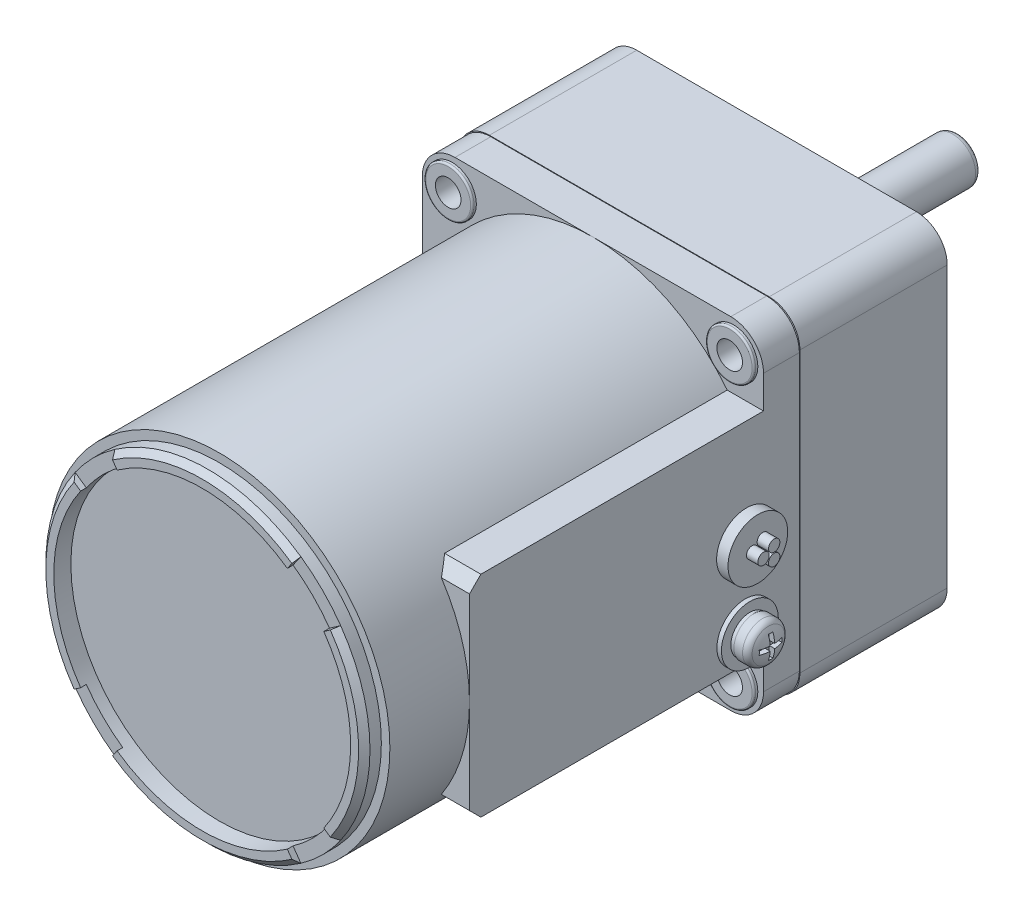
SolidWorks part; units mm, degrees
ref_plane "前视基准面" through (0, 0, 0) normal (0, 0, 1) x (1, 0, 0)
ref_plane "上视基准面" through (0, 0, 0) normal (0, 1, 0) x (1, 0, 0)
ref_plane "右视基准面" through (0, 0, 0) normal (1, 0, 0) x (0, 0, -1)
ref_plane "基准面4" through (0, 0, 0) normal (0, 0, 1) x (1, 0, 0)
sketch "草图1" plane through (0, 0, 0) normal (0, 0, 1) x (1, 0, 0)
  line L0 (-30, 24.6) -> (-30, -24.6)
  line L1 (-24.6, -30) -> (24.6, -30)
  line L2 (30, -24.6) -> (30, 24.6)
  line L3 (24.6, 30) -> (-24.6, 30)
  arc A0 (-30, -24.6) -> (-24.6, -30) centre (-24.6, -24.6) ccw
  arc A1 (24.6, -30) -> (30, -24.6) centre (24.6, -24.6) ccw
  arc A2 (30, 24.6) -> (24.6, 30) centre (24.6, 24.6) ccw
  arc A3 (-24.6, 30) -> (-30, 24.6) centre (-24.6, 24.6) ccw
extrude "凸台-拉伸1" add sketch "草图1" along normal blind 26
ref_plane "基准面5" through (0, 0, 0) normal (1, 0, 0) x (0, 0, -1)
sketch "草图2" plane through (0, 0, 0) normal (1, 0, 0) x (0, 0, -1)
  line L0 (0, 10) -> (0, 22.5)
  line L1 (0, 22.5) -> (5, 22.5)
  line L2 (6, 21.5) -> (6, 14)
  line L3 (6, 14) -> (31, 14)
  line L4 (32, 13) -> (32, 10)
  line L5 (32, 10) -> (0, 10)
  line L6 (32, 10) -> (0, 10) construction
  arc A0 (5, 22.5) -> (6, 21.5) centre (5, 21.5) cw
  arc A1 (31, 14) -> (32, 13) centre (31, 13) cw
revolve "旋转1" add sketch "草图2" angle 360 about L6 reverse direction yes
ref_plane "基准面6" through (0, 0, 26) normal (0, 0, 1) x (1, 0, 0)
sketch "草图3" plane through (0, 0, 26) normal (0, 0, 1) x (1, 0, 0)
  line L0 (-30, 24.25) -> (-30, -24.25)
  line L1 (-24.25, -30) -> (24.25, -30)
  line L2 (30, -24.25) -> (30, 24.25)
  line L3 (24.25, 30) -> (-24.25, 30)
  arc A0 (-30, -24.25) -> (-24.25, -30) centre (-24.25, -24.25) ccw
  arc A1 (24.25, -30) -> (30, -24.25) centre (24.25, -24.25) ccw
  arc A2 (30, 24.25) -> (24.25, 30) centre (24.25, 24.25) ccw
  arc A3 (-24.25, 30) -> (-30, 24.25) centre (-24.25, 24.25) ccw
extrude "凸台-拉伸2" add sketch "草图3" along normal blind 6.3
sketch "草图4" plane through (0, 0, 26) normal (0, 0, 1) x (1, 0, 0)
  line L0 (-30, 30) -> (-30, -30)
  line L1 (-30, -30) -> (30, -30)
  line L2 (30, -30) -> (30, 30)
  line L3 (30, 30) -> (-30, 30)
  line L4 (-29, 24.25) -> (-29, -24.25)
  line L5 (-24.25, -29) -> (24.25, -29)
  line L6 (29, -24.25) -> (29, 24.25)
  line L7 (24.25, 29) -> (-24.25, 29)
  arc A0 (-29, -24.25) -> (-24.25, -29) centre (-24.25, -24.25) ccw
  arc A1 (24.25, -29) -> (29, -24.25) centre (24.25, -24.25) ccw
  arc A2 (29, 24.25) -> (24.25, 29) centre (24.25, 24.25) ccw
  arc A3 (-24.25, 29) -> (-29, 24.25) centre (-24.25, 24.25) ccw
extrude "切除-拉伸1" cut sketch "草图4" against normal blind 0.1
ref_plane "基准面7" through (0, 0, 0) normal (1, 0, 0) x (0, 0, -1)
sketch "草图5" plane through (0, 0, 0) normal (1, 0, 0) x (0, 0, -1)
  line L0 (-98, 0) -> (-98, 26.1)
  line L1 (-98, 26.1) -> (-101, 26.1)
  line L2 (-101, 26.1) -> (-101, 27.5)
  line L3 (-101, 27.5) -> (-100, 28.5)
  line L4 (-100, 28.5) -> (-98, 28.5)
  line L5 (-98, 28.5) -> (-98, 30)
  line L6 (-98, 30) -> (-32.3, 30)
  line L7 (-32.3, 30) -> (-32.3, 0)
  line L8 (-32.3, 0) -> (-98, 0)
  line L9 (-32.3, 0) -> (-101, 0) construction
revolve "旋转2" add sketch "草图5" angle 360 about L9 reverse direction yes
ref_plane "基准面8" through (0, 0, 101) normal (0, 0, 1) x (1, 0, 0)
sketch "草图6" plane through (0, 0, 101) normal (0, 0, 1) x (1, 0, 0)
  line L0 (-21.3799, -14.9703) -> (-23.3458, -16.3469)
  line L1 (-16.3469, -23.3458) -> (-14.9703, -21.3799)
  line L2 (14.9703, -21.3799) -> (16.3469, -23.3458)
  line L3 (23.3458, -16.3469) -> (21.3799, -14.9703)
  line L4 (21.3799, 14.9703) -> (23.3458, 16.3469)
  line L5 (16.3469, 23.3458) -> (14.9703, 21.3799)
  line L6 (-14.9703, 21.3799) -> (-16.3469, 23.3458)
  line L7 (-23.3458, 16.3469) -> (-21.3799, 14.9703)
  arc A0 (-21.3799, 14.9703) -> (-21.3799, -14.9703) centre (0, 0) ccw
  arc A1 (-23.3458, -16.3469) -> (-16.3469, -23.3458) centre (0, 0) ccw
  arc A2 (-14.9703, -21.3799) -> (14.9703, -21.3799) centre (0, 0) ccw
  arc A3 (16.3469, -23.3458) -> (23.3458, -16.3469) centre (0, 0) ccw
  arc A4 (21.3799, -14.9703) -> (21.3799, 14.9703) centre (0, 0) ccw
  arc A5 (23.3458, 16.3469) -> (16.3469, 23.3458) centre (0, 0) ccw
  arc A6 (14.9703, 21.3799) -> (-14.9703, 21.3799) centre (0, 0) ccw
  arc A7 (-16.3469, 23.3458) -> (-23.3458, 16.3469) centre (0, 0) ccw
extrude "切除-拉伸2" cut sketch "草图6" against normal blind 1
ref_plane "基准面9" through (30, 0, 0) normal (1, 0, 0) x (0, 0, -1)
sketch "草图7" plane through (30, 0, 0) normal (1, 0, 0) x (0, 0, -1)
  line L0 (-84, -16.5) -> (-82, -18.5)
  line L1 (-82, -18.5) -> (-26, -18.5)
  line L2 (-26, -18.5) -> (-26, 18.5)
  line L3 (-26, 18.5) -> (-82, 18.5)
  line L4 (-82, 18.5) -> (-84, 16.5)
  line L5 (-84, 16.5) -> (-84, -16.5)
extrude "凸台-拉伸3" add sketch "草图7" against normal blind 30
ref_plane "基准面10" through (0, 0, 0) normal (0.7071, 0.7071, 0) x (0, 0, -1)
sketch "草图8" plane through (0, 0, 0) normal (0.7071, 0.7071, 0) x (0, 0, -1)
  line L0 (-33, -35) -> (-33, -31.05)
  line L1 (-32.7, -30.75) -> (-32.3, -30.75)
  line L2 (-32.3, -30.75) -> (-32.3, -35)
  line L3 (-32.3, -35) -> (-33, -35)
  line L4 (-32.3, -35) -> (-33, -35) construction
  arc A0 (-33, -31.05) -> (-32.7, -30.75) centre (-32.7, -31.05) cw
revolve "旋转3" add sketch "草图8" angle 360 about L4 reverse direction yes
ref_plane "基准面11" through (0, 0, 32.3) normal (0, 0, 1) x (1, 0, 0)
sketch "草图9" plane through (0, 0, 0) normal (0, 0, 1) x (1, 0, 0)
  line L0 (24.7487, -24.7487) -> (24.7487, 975.2513)
  line L1 (24.7487, -24.7487) -> (-975.2513, -24.7487)
pattern_linear "阵列(线性)1" count 2 spacing 49.4975 along (0, 1, 0) count 2 spacing 49.4975 along (-1, 0, 0) of "旋转3"
ref_plane "基准面12" through (0, 0, 0) normal (0, 1, 0) x (1, 0, 0)
sketch "草图10" plane through (0, 0, 0) normal (0, 1, 0) x (1, 0, 0)
  line L0 (32, -35.3) -> (32, -40.55)
  line L1 (32, -40.55) -> (30, -40.55)
  line L2 (30, -40.55) -> (30, -35.3)
  line L3 (30, -35.3) -> (32, -35.3)
  line L4 (30, -35.3) -> (32, -35.3) construction
revolve "旋转4" add sketch "草图10" angle 360 about L4 reverse direction yes
ref_plane "基准面13" through (32, 0, 0) normal (1, 0, 0) x (0, 0, -1)
sketch "草图11" plane through (32, 0, 0) normal (1, 0, 0) x (0, 0, -1)
  circle A0 centre (-36.3, 0) radius 1
extrude "凸台-拉伸4" add sketch "草图11" along normal blind 2
ref_plane "基准面14" through (32, 0, 0) normal (1, 0, 0) x (0, 0, -1)
sketch "草图12" plane through (32, 0, 0) normal (1, 0, 0) x (0, 0, -1)
  circle A0 centre (-34.425, -1.0825) radius 1
extrude "凸台-拉伸5" add sketch "草图12" along normal blind 2
ref_plane "基准面15" through (32, 0, 0) normal (1, 0, 0) x (0, 0, -1)
sketch "草图13" plane through (32, 0, 0) normal (1, 0, 0) x (0, 0, -1)
  circle A0 centre (-34.425, 1.0825) radius 1
extrude "凸台-拉伸6" add sketch "草图13" along normal blind 2
ref_plane "基准面16" through (0, -13.5, 0) normal (0, 1, 0) x (1, 0, 0)
sketch "草图14" plane through (0, -13.5, 0) normal (0, 1, 0) x (1, 0, 0)
  line L0 (33.0131, -39) -> (31.5, -39)
  line L1 (31.5, -39) -> (31.5, -38.85)
  line L2 (31.5, -38.85) -> (30.8, -38.85)
  line L3 (30.8, -38.85) -> (30.8, -40.5)
  line L4 (30.8, -40.5) -> (30, -40.5)
  line L5 (30, -40.5) -> (30, -35.5)
  line L6 (30, -35.5) -> (34.8, -35.5)
  line L7 (30, -35.5) -> (34.8, -35.5) construction
  arc A0 (34.8, -35.5) -> (34.0663, -38.375) centre (28.8, -35.5) cw
  arc A1 (34.0663, -38.375) -> (33.0131, -39) centre (33.0131, -37.8) cw
revolve "旋转5" add sketch "草图14" angle 360 about L7 reverse direction yes
ref_plane "基准面17" through (34.8, 0, 0) normal (1, 0, 0) x (0, 0, -1)
sketch "草图15" plane through (34.8, 0, 0) normal (1, 0, 0) x (0, 0, -1)
  line L0 (-37.5, -13.1) -> (-37.5, -13.9)
  line L1 (-37.5, -13.9) -> (-35.9, -13.9)
  line L2 (-35.9, -13.9) -> (-35.9, -15.5)
  line L3 (-35.9, -15.5) -> (-35.1, -15.5)
  line L4 (-35.1, -15.5) -> (-35.1, -13.9)
  line L5 (-35.1, -13.9) -> (-33.5, -13.9)
  line L6 (-33.5, -13.9) -> (-33.5, -13.1)
  line L7 (-33.5, -13.1) -> (-35.1, -13.1)
  line L8 (-35.1, -13.1) -> (-35.1, -11.5)
  line L9 (-35.1, -11.5) -> (-35.9, -11.5)
  line L10 (-35.9, -11.5) -> (-35.9, -13.1)
  line L11 (-35.9, -13.1) -> (-37.5, -13.1)
extrude "切除-拉伸3" cut sketch "草图15" against normal blind 1
ref_plane "基准面18" through (0, 0, 0) normal (0.7071, 0.7071, 0) x (0, 0, -1)
sketch "草图16" plane through (0, 0, 0) normal (0.7071, 0.7071, 0) x (0, 0, -1)
  line L0 (-33, -35) -> (-33, -32.75)
  line L1 (-33, -32.75) -> (0, -32.75)
  line L2 (0, -32.75) -> (0, -35)
  line L3 (0, -35) -> (-33, -35)
  line L4 (0, -35) -> (-33, -35) construction
revolve "切除-旋转1" cut sketch "草图16" angle 360 about L4 reverse direction yes
ref_plane "基准面19" through (0, 0, 33) normal (0, 0, 1) x (1, 0, 0)
sketch "草图17" plane through (0, 0, 0) normal (0, 0, 1) x (1, 0, 0)
  line L0 (24.7487, -24.7487) -> (24.7487, 975.2513)
  line L1 (24.7487, -24.7487) -> (-975.2513, -24.7487)
pattern_linear "阵列(线性)2" count 2 spacing 49.4975 along (0, 1, 0) count 2 spacing 49.4975 along (-1, 0, 0) of "切除-旋转1"
ref_plane "基准面20" through (0, 0, 0) normal (0, 0, 1) x (1, 0, 0)
ref_plane "基准面21" through (0, 0, 0) normal (0, 0, 1) x (1, 0, 0)
ref_plane "基准面22" through (0, 0, 34.8) normal (0, 0, 1) x (1, 0, 0)
ref_plane "基准面23" through (0, 0, 33) normal (0, 0, 1) x (1, 0, 0)
ref_plane "基准面24" through (0, 0, 34.8) normal (0, 0, 1) x (1, 0, 0)
ref_plane "to_motor XY" through (0, 0, 0) normal (0, 0, -1) x (-1, 0, 0)
ref_plane "to_motor XZ" through (0, 10, 0) normal (0, 1, 0) x (1, 0, 0)
ref_plane "to_motor YZ" through (0, 0, 0) normal (1, 0, 0) x (0, 0, -1)
ref_axis "to_motor X" through (-80.9, 10, 0) along (1, 0, 0)
ref_axis "to_motor Y" through (0, 50, 0) along (0, -1, 0)
ref_axis "to_motor Z" through (0, 10, -80.9) along (0, 0, 1)
sketch3d "to_motor"
  point P0 (0, 10, 0)
ref_plane "to_motor_r XY" through (0, 0, 0) normal (0, 0, -1) x (-1, 0, 0)
ref_plane "to_motor_r XZ" through (0, -10, 0) normal (0, 1, 0) x (1, 0, 0)
ref_plane "to_motor_r YZ" through (0, 0, 0) normal (1, 0, 0) x (0, 0, -1)
ref_axis "to_motor_r X" through (-80.9, -10, 0) along (1, 0, 0)
ref_axis "to_motor_r Y" through (0, 50, 0) along (0, -1, 0)
ref_axis "to_motor_r Z" through (0, -10, -80.9) along (0, 0, 1)
sketch3d "to_motor_r"
  point P0 (0, -10, 0)
ref_plane "to_bolt_inner4 XY" through (0, 0, 0) normal (0, 0, -1) x (-1, 0, 0)
ref_plane "to_bolt_inner4 XZ" through (0, 24.7487, 0) normal (0, 1, 0) x (1, 0, 0)
ref_plane "to_bolt_inner4 YZ" through (-24.7487, 0, 0) normal (1, 0, 0) x (0, 0, -1)
ref_axis "to_bolt_inner4 X" through (-80.9, 24.7487, 0) along (1, 0, 0)
ref_axis "to_bolt_inner4 Y" through (-24.7487, 50, 0) along (0, -1, 0)
ref_axis "to_bolt_inner4 Z" through (-24.7487, 24.7487, -80.9) along (0, 0, 1)
sketch3d "to_bolt_inner4"
  point P0 (-24.7487, 24.7487, 0)
ref_plane "to_bolt_inner2 XY" through (0, 0, 0) normal (0, 0, -1) x (-1, 0, 0)
ref_plane "to_bolt_inner2 XZ" through (0, -24.7487, 0) normal (0, 1, 0) x (1, 0, 0)
ref_plane "to_bolt_inner2 YZ" through (-24.7487, 0, 0) normal (1, 0, 0) x (0, 0, -1)
ref_axis "to_bolt_inner2 X" through (-80.9, -24.7487, 0) along (1, 0, 0)
ref_axis "to_bolt_inner2 Y" through (-24.7487, 50, 0) along (0, -1, 0)
ref_axis "to_bolt_inner2 Z" through (-24.7487, -24.7487, -80.9) along (0, 0, 1)
sketch3d "to_bolt_inner2"
  point P0 (-24.7487, -24.7487, 0)
ref_plane "to_bolt_inner3 XY" through (0, 0, 0) normal (0, 0, -1) x (-1, 0, 0)
ref_plane "to_bolt_inner3 XZ" through (0, -24.7487, 0) normal (0, 1, 0) x (1, 0, 0)
ref_plane "to_bolt_inner3 YZ" through (24.7487, 0, 0) normal (1, 0, 0) x (0, 0, -1)
ref_axis "to_bolt_inner3 X" through (-80.9, -24.7487, 0) along (1, 0, 0)
ref_axis "to_bolt_inner3 Y" through (24.7487, 50, 0) along (0, -1, 0)
ref_axis "to_bolt_inner3 Z" through (24.7487, -24.7487, -80.9) along (0, 0, 1)
sketch3d "to_bolt_inner3"
  point P0 (24.7487, -24.7487, 0)
ref_plane "to_bolt_inner1 XY" through (0, 0, 0) normal (0, 0, -1) x (-1, 0, 0)
ref_plane "to_bolt_inner1 XZ" through (0, 24.7487, 0) normal (0, 1, 0) x (1, 0, 0)
ref_plane "to_bolt_inner1 YZ" through (24.7487, 0, 0) normal (1, 0, 0) x (0, 0, -1)
ref_axis "to_bolt_inner1 X" through (-80.9, 24.7487, 0) along (1, 0, 0)
ref_axis "to_bolt_inner1 Y" through (24.7487, 50, 0) along (0, -1, 0)
ref_axis "to_bolt_inner1 Z" through (24.7487, 24.7487, -80.9) along (0, 0, 1)
sketch3d "to_bolt_inner1"
  point P0 (24.7487, 24.7487, 0)
ref_plane "to_bolt_outer4 XY" through (0, 0, 34.8) normal (0, 0, 1) x (1, 0, 0)
ref_plane "to_bolt_outer4 XZ" through (0, 24.7487, 0) normal (0, -1, 0) x (-1, 0, 0)
ref_plane "to_bolt_outer4 YZ" through (-24.7487, 0, 0) normal (1, 0, 0) x (0, 0, -1)
ref_axis "to_bolt_outer4 X" through (-80.9, 24.7487, 34.8) along (1, 0, 0)
ref_axis "to_bolt_outer4 Y" through (-24.7487, -50, 34.8) along (0, 1, 0)
ref_axis "to_bolt_outer4 Z" through (-24.7487, 24.7487, 80.9) along (0, 0, -1)
sketch3d "to_bolt_outer4"
  point P0 (-24.7487, 24.7487, 34.8)
ref_plane "to_bolt_outer2 XY" through (0, 0, 34.8) normal (0, 0, 1) x (1, 0, 0)
ref_plane "to_bolt_outer2 XZ" through (0, -24.7487, 0) normal (0, -1, 0) x (-1, 0, 0)
ref_plane "to_bolt_outer2 YZ" through (-24.7487, 0, 0) normal (1, 0, 0) x (0, 0, -1)
ref_axis "to_bolt_outer2 X" through (-80.9, -24.7487, 34.8) along (1, 0, 0)
ref_axis "to_bolt_outer2 Y" through (-24.7487, -50, 34.8) along (0, 1, 0)
ref_axis "to_bolt_outer2 Z" through (-24.7487, -24.7487, 80.9) along (0, 0, -1)
sketch3d "to_bolt_outer2"
  point P0 (-24.7487, -24.7487, 34.8)
ref_plane "to_bolt_outer3 XY" through (0, 0, 34.8) normal (0, 0, 1) x (1, 0, 0)
ref_plane "to_bolt_outer3 XZ" through (0, -24.7487, 0) normal (0, -1, 0) x (-1, 0, 0)
ref_plane "to_bolt_outer3 YZ" through (24.7487, 0, 0) normal (1, 0, 0) x (0, 0, -1)
ref_axis "to_bolt_outer3 X" through (-80.9, -24.7487, 34.8) along (1, 0, 0)
ref_axis "to_bolt_outer3 Y" through (24.7487, -50, 34.8) along (0, 1, 0)
ref_axis "to_bolt_outer3 Z" through (24.7487, -24.7487, 80.9) along (0, 0, -1)
sketch3d "to_bolt_outer3"
  point P0 (24.7487, -24.7487, 34.8)
ref_plane "to_bolt_outer1 XY" through (0, 0, 34.8) normal (0, 0, 1) x (1, 0, 0)
ref_plane "to_bolt_outer1 XZ" through (0, 24.7487, 0) normal (0, -1, 0) x (-1, 0, 0)
ref_plane "to_bolt_outer1 YZ" through (24.7487, 0, 0) normal (1, 0, 0) x (0, 0, -1)
ref_axis "to_bolt_outer1 X" through (-80.9, 24.7487, 34.8) along (1, 0, 0)
ref_axis "to_bolt_outer1 Y" through (24.7487, -50, 34.8) along (0, 1, 0)
ref_axis "to_bolt_outer1 Z" through (24.7487, 24.7487, 80.9) along (0, 0, -1)
sketch3d "to_bolt_outer1"
  point P0 (24.7487, 24.7487, 34.8)
ref_plane "to_washer1 XY" through (0, 0, 33) normal (0, 0, 1) x (1, 0, 0)
ref_plane "to_washer1 XZ" through (0, 24.7487, 0) normal (0, -1, 0) x (-1, 0, 0)
ref_plane "to_washer1 YZ" through (24.7487, 0, 0) normal (1, 0, 0) x (0, 0, -1)
ref_axis "to_washer1 X" through (-80.9, 24.7487, 33) along (1, 0, 0)
ref_axis "to_washer1 Y" through (24.7487, -50, 33) along (0, 1, 0)
ref_axis "to_washer1 Z" through (24.7487, 24.7487, 80.9) along (0, 0, -1)
sketch3d "to_washer1"
  point P0 (24.7487, 24.7487, 33)
ref_plane "to_washer3 XY" through (0, 0, 33) normal (0, 0, 1) x (1, 0, 0)
ref_plane "to_washer3 XZ" through (0, -24.7487, 0) normal (0, -1, 0) x (-1, 0, 0)
ref_plane "to_washer3 YZ" through (24.7487, 0, 0) normal (1, 0, 0) x (0, 0, -1)
ref_axis "to_washer3 X" through (-80.9, -24.7487, 33) along (1, 0, 0)
ref_axis "to_washer3 Y" through (24.7487, -50, 33) along (0, 1, 0)
ref_axis "to_washer3 Z" through (24.7487, -24.7487, 80.9) along (0, 0, -1)
sketch3d "to_washer3"
  point P0 (24.7487, -24.7487, 33)
ref_plane "to_washer2 XY" through (0, 0, 33) normal (0, 0, 1) x (1, 0, 0)
ref_plane "to_washer2 XZ" through (0, -24.7487, 0) normal (0, -1, 0) x (-1, 0, 0)
ref_plane "to_washer2 YZ" through (-24.7487, 0, 0) normal (1, 0, 0) x (0, 0, -1)
ref_axis "to_washer2 X" through (-80.9, -24.7487, 33) along (1, 0, 0)
ref_axis "to_washer2 Y" through (-24.7487, -50, 33) along (0, 1, 0)
ref_axis "to_washer2 Z" through (-24.7487, -24.7487, 80.9) along (0, 0, -1)
sketch3d "to_washer2"
  point P0 (-24.7487, -24.7487, 33)
ref_plane "to_washer4 XY" through (0, 0, 33) normal (0, 0, 1) x (1, 0, 0)
ref_plane "to_washer4 XZ" through (0, 24.7487, 0) normal (0, -1, 0) x (-1, 0, 0)
ref_plane "to_washer4 YZ" through (-24.7487, 0, 0) normal (1, 0, 0) x (0, 0, -1)
ref_axis "to_washer4 X" through (-80.9, 24.7487, 33) along (1, 0, 0)
ref_axis "to_washer4 Y" through (-24.7487, -50, 33) along (0, 1, 0)
ref_axis "to_washer4 Z" through (-24.7487, 24.7487, 80.9) along (0, 0, -1)
sketch3d "to_washer4"
  point P0 (-24.7487, 24.7487, 33)
ref_plane "to_nut4 XY" through (0, 0, 34.8) normal (0, 0, 1) x (1, 0, 0)
ref_plane "to_nut4 XZ" through (0, 24.7487, 0) normal (0, -1, 0) x (-1, 0, 0)
ref_plane "to_nut4 YZ" through (-24.7487, 0, 0) normal (1, 0, 0) x (0, 0, -1)
ref_axis "to_nut4 X" through (-80.9, 24.7487, 34.8) along (1, 0, 0)
ref_axis "to_nut4 Y" through (-24.7487, -50, 34.8) along (0, 1, 0)
ref_axis "to_nut4 Z" through (-24.7487, 24.7487, 80.9) along (0, 0, -1)
sketch3d "to_nut4"
  point P0 (-24.7487, 24.7487, 34.8)
ref_plane "to_nut1 XY" through (0, 0, 34.8) normal (0, 0, 1) x (1, 0, 0)
ref_plane "to_nut1 XZ" through (0, 24.7487, 0) normal (0, -1, 0) x (-1, 0, 0)
ref_plane "to_nut1 YZ" through (24.7487, 0, 0) normal (1, 0, 0) x (0, 0, -1)
ref_axis "to_nut1 X" through (-80.9, 24.7487, 34.8) along (1, 0, 0)
ref_axis "to_nut1 Y" through (24.7487, -50, 34.8) along (0, 1, 0)
ref_axis "to_nut1 Z" through (24.7487, 24.7487, 80.9) along (0, 0, -1)
sketch3d "to_nut1"
  point P0 (24.7487, 24.7487, 34.8)
ref_plane "to_nut3 XY" through (0, 0, 34.8) normal (0, 0, 1) x (1, 0, 0)
ref_plane "to_nut3 XZ" through (0, -24.7487, 0) normal (0, -1, 0) x (-1, 0, 0)
ref_plane "to_nut3 YZ" through (24.7487, 0, 0) normal (1, 0, 0) x (0, 0, -1)
ref_axis "to_nut3 X" through (-80.9, -24.7487, 34.8) along (1, 0, 0)
ref_axis "to_nut3 Y" through (24.7487, -50, 34.8) along (0, 1, 0)
ref_axis "to_nut3 Z" through (24.7487, -24.7487, 80.9) along (0, 0, -1)
sketch3d "to_nut3"
  point P0 (24.7487, -24.7487, 34.8)
ref_plane "to_nut2 XY" through (0, 0, 34.8) normal (0, 0, 1) x (1, 0, 0)
ref_plane "to_nut2 XZ" through (0, -24.7487, 0) normal (0, -1, 0) x (-1, 0, 0)
ref_plane "to_nut2 YZ" through (-24.7487, 0, 0) normal (1, 0, 0) x (0, 0, -1)
ref_axis "to_nut2 X" through (-80.9, -24.7487, 34.8) along (1, 0, 0)
ref_axis "to_nut2 Y" through (-24.7487, -50, 34.8) along (0, 1, 0)
ref_axis "to_nut2 Z" through (-24.7487, -24.7487, 80.9) along (0, 0, -1)
sketch3d "to_nut2"
  point P0 (-24.7487, -24.7487, 34.8)
